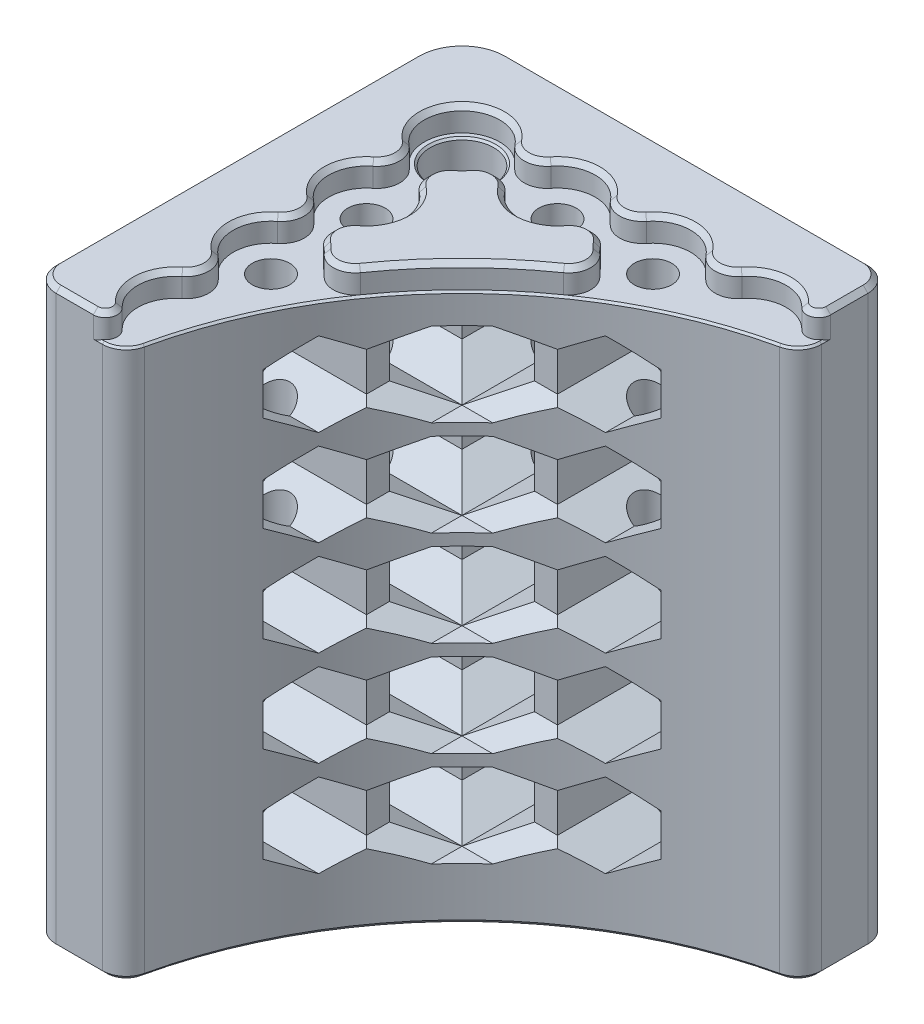
SolidWorks part; units mm, degrees
material "PET"
ref_plane "Front Plane" through (0, 0, 0) normal (0, 0, 1) x (1, 0, 0)
ref_plane "Top Plane" through (0, 0, 0) normal (0, 1, 0) x (1, 0, 0)
ref_plane "Right Plane" through (0, 0, 0) normal (1, 0, 0) x (0, 0, -1)
sketch "Sketch2" plane through (0, 0, 0) normal (0, 1, 0) x (1, 0, 0)
  line L0 (0, 0) -> (0, -53.975)
  line L1 (0, 0) -> (53.975, 0)
  line L2 (57.15, -3.175) -> (57.15, -11.935)
  line L3 (3.175, -57.15) -> (9.3269, -57.15)
  circle A0 centre (66.675, -66.675) radius 55.5625
  circle A1 centre (53.975, -3.175) radius 3.175
  circle A2 centre (53.975, -9.3269) radius 3.175
  circle A3 centre (3.175, -53.975) radius 3.175
  circle A4 centre (9.3269, -53.975) radius 3.175
  circle A5 centre (6.35, -6.35) radius 6.35
  dimension "D2" = 111.125
  dimension "D3" = 6.35
  dimension "D6" = 6.35
  dimension "D7" = 12.7
  dimension "D1" = 53.975
  dimension "D4" = 66.675
  dimension "D5" = 66.675
extrude "Boss-Extrude1" add sketch "Sketch2" along normal blind 76.2 contours A4 A0 A2 A1 L1 L0 A3 | A4 A3 | A4 A3 L3 | A4 A3 | A2 A1 | A2 L2 A1 | A2 A1 | A3 A4 | A1 A2 | A5 region at (20.4992, 0, 20.4992) region at (6.35, 0, 6.35) region at (3.1546, 0, 53.975) region at (53.975, 0, 3.1546) region at (6.251, 0, 56.5266) region at (9.3473, 0, 53.975) region at (6.251, 0, 53.975) region at (56.5266, 0, 6.251) region at (53.975, 0, 6.251) region at (53.975, 0, 9.3473)
sketch "Sketch3" plane through (0, 0, 0) normal (-1, 0, 0) x (0, 0, 1)
  line L0 (6.35, 0) -> (53.975, 0) construction
  line L2 (0, 76.2) -> (0, 0) construction
  circle A0 centre (25.4, 12.7) radius 2.4892
  circle A1 centre (38.1, 12.7) radius 2.4892
  circle A2 centre (38.1, 25.4) radius 2.4892
  circle A3 centre (38.1, 38.1) radius 2.4892
  circle A4 centre (38.1, 50.8) radius 2.4892
  circle A5 centre (38.1, 63.5) radius 2.4892
  circle A6 centre (25.4, 25.4) radius 2.4892
  circle A7 centre (25.4, 38.1) radius 2.4892
  circle A8 centre (25.4, 50.8) radius 2.4892
  circle A9 centre (25.4, 63.5) radius 2.4892
  dimension "D1" = 4.9784
  dimension "D2" = 12.7
  dimension "D3" = 25.4
  dimension "D6" = 12.7
  dimension "D7" = 12.7
  dimension "D4" = 2
  dimension "D5" = 5
extrude "Cut-Extrude1" cut sketch "Sketch3" against normal blind 76.2
sketch "Sketch4" plane through (0, 0, 0) normal (0, 0, -1) x (-1, 0, 0)
  line L0 (-6.35, 0) -> (-53.975, 0) construction
  line L1 (-6.35, 76.2) -> (-6.35, 0) construction
  circle A0 centre (-25.4, 12.7) radius 2.4892
  circle A1 centre (-38.1, 12.7) radius 2.4892
  circle A2 centre (-38.1, 25.4) radius 2.4892
  circle A3 centre (-38.1, 38.1) radius 2.4892
  circle A4 centre (-38.1, 50.8) radius 2.4892
  circle A5 centre (-38.1, 63.5) radius 2.4892
  circle A6 centre (-25.4, 25.4) radius 2.4892
  circle A7 centre (-25.4, 38.1) radius 2.4892
  circle A8 centre (-25.4, 50.8) radius 2.4892
  circle A9 centre (-25.4, 63.5) radius 2.4892
  dimension "D1" = 4.9784
  dimension "D2" = 12.7
  dimension "D3" = 19.05
  dimension "D6" = 12.7
  dimension "D7" = 12.7
  dimension "D4" = 2
  dimension "D5" = 5
extrude "Cut-Extrude2" cut sketch "Sketch4" against normal blind 76.2
sketch "Sketch5" plane through (0, 76.2, 0) normal (0, 1, 0) x (1, 0, 0)
  line L0 (12.7, -12.7) -> (12.7, -25.4) construction
  line L1 (12.7, -25.4) -> (12.7, -38.1) construction
  line L2 (12.7, -12.7) -> (25.4, -12.7) construction
  line L3 (25.4, -12.7) -> (38.1, -12.7) construction
  line L4 (0, -6.35) -> (0, -53.975) construction
  line L5 (6.35, 0) -> (53.975, 0) construction
  circle A0 centre (12.7, -12.7) radius 4.2228
  circle A1 centre (25.4, -12.7) radius 2.4892
  circle A2 centre (38.1, -12.7) radius 2.4892
  circle A3 centre (12.7, -25.4) radius 2.4892
  circle A4 centre (12.7, -38.1) radius 2.4892
  dimension "D1" = 8.4455
  dimension "D2" = 4.9784
  dimension "D3" = 12.7
  dimension "D4" = 12.7
  dimension "D5" = 12.7
  dimension "D6" = 12.7
  dimension "D7" = 12.7
extrude "Cut-Extrude3" cut sketch "Sketch5" against normal through all contours A0 region at (12.7, 76.2, 12.7)
sketch "Sketch8" plane through (0, 76.2, 0) normal (0, 1, 0) x (1, 0, 0)
  circle A0 centre (12.7, -38.1) radius 2.4892 construction
  circle A1 centre (12.7, -25.4) radius 2.4892 construction
  circle A2 centre (38.1, -12.7) radius 2.4892 construction
  circle A3 centre (25.4, -12.7) radius 2.4892 construction
  circle A4 centre (12.7, -38.1) radius 2.4892
  circle A5 centre (12.7, -25.4) radius 2.4892
  circle A6 centre (38.1, -12.7) radius 2.4892
  circle A7 centre (25.4, -12.7) radius 2.4892
extrude "Cut-Extrude5" cut sketch "Sketch8" against normal blind 35.56
sketch "Sketch7" plane through (0, 76.2, 0) normal (0, 1, 0) x (1, 0, 0)
  line L0 (3.175, -57.15) -> (9.3269, -57.15) construction
  line L1 (6.35, 0) -> (53.975, 0) construction
  line L2 (57.15, -3.175) -> (57.15, -9.3269) construction
  line L3 (0, -6.35) -> (0, -53.975) construction
  line L4 (6.35, 0) -> (53.975, 0)
  line L5 (57.15, -3.175) -> (57.15, -9.3269)
  line L6 (3.175, -57.15) -> (9.3269, -57.15)
  line L7 (0, -6.35) -> (0, -53.975)
  circle A0 centre (12.7, -12.7) radius 5.0165
  circle A1 centre (25.4, -12.7) radius 5.0165
  circle A2 centre (38.1, -12.7) radius 5.0165
  circle A3 centre (12.7, -25.4) radius 5.0165
  circle A4 centre (12.7, -38.1) radius 5.0165
  arc A5 (9.6076, -21.45) -> (9.6076, -16.65) centre (7.7287, -19.05) ccw
  arc A6 (9.6076, -34.15) -> (9.6076, -29.35) centre (7.7287, -31.75) ccw
  arc A7 (29.35, -9.6076) -> (34.15, -9.6076) centre (31.75, -7.7287) ccw
  arc A8 (16.65, -9.6076) -> (21.45, -9.6076) centre (19.05, -7.7287) ccw
  arc A9 (9.6076, -46.85) -> (9.6076, -42.05) centre (7.7287, -44.45) ccw
  arc A10 (8.1249, -57.15) -> (9.2247, -54.4177) centre (8.1249, -55.5625) ccw
  arc A11 (9.6076, -46.85) -> (9.2247, -54.4177) centre (12.7, -50.8) ccw
  arc A12 (57.15, -3.175) -> (53.975, 0) centre (53.975, -3.175) ccw construction
  arc A13 (6.35, 0) -> (0, -6.35) centre (6.35, -6.35) ccw construction
  circle A14 centre (12.7, -25.4) radius 2.4892 construction
  arc A15 (9.3269, -57.15) -> (12.4268, -54.6615) centre (9.3269, -53.975) ccw construction
  arc A16 (54.6615, -12.4268) -> (12.4268, -54.6615) centre (66.675, -66.675) ccw construction
  arc A17 (0, -53.975) -> (3.175, -57.15) centre (3.175, -53.975) ccw construction
  arc A18 (57.15, -3.175) -> (53.975, 0) centre (53.975, -3.175) ccw
  arc A19 (6.35, 0) -> (0, -6.35) centre (6.35, -6.35) ccw
  arc A20 (54.6615, -12.4268) -> (57.15, -9.3269) centre (53.975, -9.3269) ccw
  arc A21 (9.3269, -57.15) -> (12.4268, -54.6615) centre (9.3269, -53.975) ccw
  arc A22 (54.6615, -12.4268) -> (12.4268, -54.6615) centre (66.675, -66.675) ccw
  arc A23 (0, -53.975) -> (3.175, -57.15) centre (3.175, -53.975) ccw
  arc A24 (54.4177, -9.2247) -> (46.85, -9.6076) centre (50.8, -12.7) ccw
  arc A25 (54.4177, -9.2247) -> (57.15, -8.1249) centre (55.5625, -8.1249) ccw
  arc A26 (42.05, -9.6076) -> (46.85, -9.6076) centre (44.45, -7.7287) ccw
  arc A27 (55.7937, -11.9294) -> (11.9294, -55.7937) centre (66.675, -66.675) ccw
  arc A28 (34.5329, -21.0421) -> (34.7825, -16.4629) centre (32.8508, -18.654) ccw
  arc A29 (16.4629, -34.7825) -> (21.0421, -34.5329) centre (18.654, -32.8508) ccw
  arc A30 (34.0868, -15.7099) -> (29.4132, -15.7099) centre (31.75, -17.4625) ccw
  arc A31 (15.7099, -29.4132) -> (15.7099, -34.0868) centre (17.4625, -31.75) ccw
  arc A32 (15.7099, -16.7132) -> (15.7099, -21.3868) centre (17.4625, -19.05) ccw
  arc A33 (21.3868, -15.7099) -> (16.7132, -15.7099) centre (19.05, -17.4625) ccw
  circle A34 centre (12.7, -38.1) radius 2.4892 construction
  circle A38 centre (38.1, -12.7) radius 2.4892 construction
  circle A39 centre (25.4, -12.7) radius 2.4892 construction
  arc A40 (54.6615, -12.4268) -> (57.15, -9.3269) centre (53.975, -9.3269) ccw construction
  circle M5 centre (12.7, -12.7) radius 4.2228
  arc M6 (54.6615, -12.4268) -> (57.15, -9.3269) centre (53.975, -9.3269) ccw
  line M7 (57.15, -9.3269) -> (57.15, -3.175)
  arc M14 (9.3269, -57.15) -> (12.4268, -54.6615) centre (9.3269, -53.975) ccw
  arc M15 (12.4268, -54.6615) -> (54.6615, -12.4268) centre (66.675, -66.675) cw
  circle M59 centre (12.7, -38.1) radius 2.4892
  circle M60 centre (25.4, -12.7) radius 2.4892
  circle M61 centre (38.1, -12.7) radius 2.4892
  circle M62 centre (12.7, -25.4) radius 2.4892
  dimension "D1" = 10.033
  dimension "D2" = 6.096
  dimension "D3" = 3.175
  dimension "D4" = 111.633
  dimension "D5" = 5.842
extrude "Cut-Extrude8" cut sketch "Sketch7" against normal blind 3.175 contours A0 M5 | A32 A0 A5 A3 | A3 M62 | A31 A3 A6 A4 | A4 M59 | A29 A4 A9 A11 A10 L6 A27 M14 | A27 A21 M6 M15 | A33 A1 A8 A0 | A1 M60 | A30 A2 A7 A1 | A28 A27 A20 A25 A24 A26 A2 M7 | A2 M61 region at (47.9531, 76.2, 12.1291) region at (12.1291, 76.2, 47.9531) region at (55.2271, 76.2, 12.177) region at (42.7083, 76.2, 11.1107) region at (31.75, 76.2, 12.6504) region at (7.8254, 76.2, 38.1) region at (30.0083, 76.2, 11.1107) region at (12.6504, 76.2, 31.75) region at (19.05, 76.2, 12.6504) region at (7.8254, 76.2, 25.4) region at (17.3083, 76.2, 11.1107) region at (12.6504, 76.2, 19.05)
ref_plane "Plane1" through (57.15, 0, 0) normal (1, 0, 0) x (0, 0, -1)
ref_plane "Plane2" through (0, 0, 57.15) normal (0, 0, 1) x (1, 0, 0)
sketch "Sketch9" plane through (57.15, 0, 0) normal (1, 0, 0) x (0, 0, -1)
  line L1 (-42.926, 66.2863) -> (-42.926, 60.7137)
  line L2 (-42.926, 60.7137) -> (-38.1, 57.9274)
  line L3 (-38.1, 57.9274) -> (-33.274, 60.7137)
  line L4 (-33.274, 60.7137) -> (-33.274, 66.2863)
  line L5 (-33.274, 66.2863) -> (-38.1, 69.0726)
  line L6 (-38.1, 69.0726) -> (-42.926, 66.2863)
  line L7 (-20.574, 66.2863) -> (-25.4, 69.0726)
  line L8 (-25.4, 69.0726) -> (-30.226, 66.2863)
  line L9 (-30.226, 66.2863) -> (-30.226, 60.7137)
  line L10 (-30.226, 60.7137) -> (-25.4, 57.9274)
  line L11 (-25.4, 57.9274) -> (-20.574, 60.7137)
  line L12 (-20.574, 60.7137) -> (-20.574, 66.2863)
  line L13 (-20.574, 53.5863) -> (-25.4, 56.3726)
  line L14 (-25.4, 56.3726) -> (-30.226, 53.5863)
  line L15 (-30.226, 53.5863) -> (-30.226, 48.0137)
  line L16 (-30.226, 48.0137) -> (-25.4, 45.2274)
  line L17 (-25.4, 45.2274) -> (-20.574, 48.0137)
  line L18 (-20.574, 48.0137) -> (-20.574, 53.5863)
  line L19 (-33.274, 53.5863) -> (-38.1, 56.3726)
  line L20 (-38.1, 56.3726) -> (-42.926, 53.5863)
  line L21 (-42.926, 53.5863) -> (-42.926, 48.0137)
  line L22 (-42.926, 48.0137) -> (-38.1, 45.2274)
  line L23 (-38.1, 45.2274) -> (-33.274, 48.0137)
  line L24 (-33.274, 48.0137) -> (-33.274, 53.5863)
  line L25 (-38.1, 43.6726) -> (-42.926, 40.8863)
  line L26 (-42.926, 40.8863) -> (-42.926, 35.3137)
  line L27 (-42.926, 35.3137) -> (-38.1, 32.5274)
  line L28 (-38.1, 32.5274) -> (-33.274, 35.3137)
  line L29 (-33.274, 35.3137) -> (-33.274, 40.8863)
  line L30 (-33.274, 40.8863) -> (-38.1, 43.6726)
  line L31 (-20.574, 40.8863) -> (-25.4, 43.6726)
  line L32 (-25.4, 43.6726) -> (-30.226, 40.8863)
  line L33 (-30.226, 40.8863) -> (-30.226, 35.3137)
  line L34 (-30.226, 35.3137) -> (-25.4, 32.5274)
  line L35 (-25.4, 32.5274) -> (-20.574, 35.3137)
  line L36 (-20.574, 35.3137) -> (-20.574, 40.8863)
  line L37 (-20.574, 28.1863) -> (-25.4, 30.9726)
  line L38 (-25.4, 30.9726) -> (-30.226, 28.1863)
  line L39 (-30.226, 28.1863) -> (-30.226, 22.6137)
  line L40 (-30.226, 22.6137) -> (-25.4, 19.8274)
  line L41 (-25.4, 19.8274) -> (-20.574, 22.6137)
  line L42 (-20.574, 22.6137) -> (-20.574, 28.1863)
  line L43 (-33.274, 28.1863) -> (-38.1, 30.9726)
  line L44 (-38.1, 30.9726) -> (-42.926, 28.1863)
  line L45 (-42.926, 28.1863) -> (-42.926, 22.6137)
  line L46 (-42.926, 22.6137) -> (-38.1, 19.8274)
  line L47 (-38.1, 19.8274) -> (-33.274, 22.6137)
  line L48 (-33.274, 22.6137) -> (-33.274, 28.1863)
  line L49 (-38.1, 18.2726) -> (-42.926, 15.4863)
  line L50 (-42.926, 15.4863) -> (-42.926, 9.9137)
  line L51 (-42.926, 9.9137) -> (-38.1, 7.1274)
  line L52 (-38.1, 7.1274) -> (-33.274, 9.9137)
  line L53 (-33.274, 9.9137) -> (-33.274, 15.4863)
  line L54 (-33.274, 15.4863) -> (-38.1, 18.2726)
  line L55 (-20.574, 15.4863) -> (-25.4, 18.2726)
  line L56 (-25.4, 18.2726) -> (-30.226, 15.4863)
  line L57 (-30.226, 15.4863) -> (-30.226, 9.9137)
  line L58 (-30.226, 9.9137) -> (-25.4, 7.1274)
  line L59 (-25.4, 7.1274) -> (-20.574, 9.9137)
  line L60 (-20.574, 9.9137) -> (-20.574, 15.4863)
  circle A0 centre (-38.1, 63.5) radius 4.826 construction
  circle A1 centre (-25.4, 63.5) radius 4.826 construction
  circle A2 centre (-25.4, 50.8) radius 4.826 construction
  circle A3 centre (-38.1, 50.8) radius 4.826 construction
  circle A4 centre (-38.1, 38.1) radius 4.826 construction
  circle A5 centre (-25.4, 38.1) radius 4.826 construction
  circle A6 centre (-25.4, 25.4) radius 4.826 construction
  circle A7 centre (-38.1, 25.4) radius 4.826 construction
  circle A8 centre (-38.1, 12.7) radius 4.826 construction
  circle A9 centre (-25.4, 12.7) radius 4.826 construction
  point P91 (-33.274, 38.1)
  dimension "D1" = 9.652
extrude "Cut-Extrude6" cut sketch "Sketch9" against normal offset from surface (47.625 mm away) 9.525 up to face at (0, 63.5, 40.5892)
chamfer "Chamfer3" distance 0.254 angle 45 6 edges at (12.7, 73.025, 16.9228) (57.15, 73.025, 8.7259) (56.4509, 73.025, 11.3145) (8.7259, 73.025, 57.15) (27.3864, 73.025, 27.3864) (11.3145, 73.025, 56.4509)
chamfer "Chamfer4" distance 0.635 angle 45 45 edges at (34.4154, 76.2, 16.1042) (31.75, 76.2, 14.5415) (35.7675, 76.2, 18.813) (25.4, 76.2, 17.7165) (19.05, 76.2, 14.5415) (16.2472, 76.2, 16.2472) (27.2068, 76.2, 27.2068) (18.813, 76.2, 35.7675) (16.1042, 76.2, 34.4154) (14.5415, 76.2, 31.75) (17.7165, 76.2, 25.4) (14.5415, 76.2, 19.05) (10.7767, 76.2, 19.05) (9.1528, 76.2, 9.1528) (19.05, 76.2, 10.7767) (25.4, 76.2, 7.6835) (31.75, 76.2, 10.7767) (38.1, 76.2, 7.6835) (44.45, 76.2, 10.7767) (50.5465, 76.2, 7.6899) (56.1553, 76.2, 9.5976) (57.15, 76.2, 5.65) (56.2201, 76.2, 0.9299) (30.1625, 76.2, 0) (1.8599, 76.2, 1.8599) (0, 76.2, 30.1625) (0.9299, 76.2, 56.2201) (5.65, 76.2, 57.15) (9.5976, 76.2, 56.1553) (7.6899, 76.2, 50.5465) (10.7767, 76.2, 44.45) (7.6835, 76.2, 38.1) (10.7767, 76.2, 31.75) (7.6835, 76.2, 25.4) (12.7, 0, 16.9228) (56.2201, 0, 0.9299) (57.15, 0, 6.251) (56.4509, 0, 11.3145) (30.1625, 0, 0) (1.8599, 0, 1.8599) (0, 0, 30.1625) (0.9299, 0, 56.2201) (6.251, 0, 57.15) (27.3864, 0, 27.3864) (11.3145, 0, 56.4509)
sketch "Sketch13" plane through (0, 0, 57.15) normal (0, 0, 1) x (1, 0, 0)
  line L1 (25.4, 69.0726) -> (20.574, 66.2863)
  line L2 (20.574, 66.2863) -> (20.574, 60.7137)
  line L3 (20.574, 60.7137) -> (25.4, 57.9274)
  line L4 (25.4, 57.9274) -> (30.226, 60.7137)
  line L5 (30.226, 60.7137) -> (30.226, 66.2863)
  line L6 (30.226, 66.2863) -> (25.4, 69.0726)
  line L7 (42.926, 66.2863) -> (38.1, 69.0726)
  line L8 (38.1, 69.0726) -> (33.274, 66.2863)
  line L9 (33.274, 66.2863) -> (33.274, 60.7137)
  line L10 (33.274, 60.7137) -> (38.1, 57.9274)
  line L11 (38.1, 57.9274) -> (42.926, 60.7137)
  line L12 (42.926, 60.7137) -> (42.926, 66.2863)
  line L13 (42.926, 53.5863) -> (38.1, 56.3726)
  line L14 (38.1, 56.3726) -> (33.274, 53.5863)
  line L15 (33.274, 53.5863) -> (33.274, 48.0137)
  line L16 (33.274, 48.0137) -> (38.1, 45.2274)
  line L17 (38.1, 45.2274) -> (42.926, 48.0137)
  line L18 (42.926, 48.0137) -> (42.926, 53.5863)
  line L19 (30.226, 53.5863) -> (25.4, 56.3726)
  line L20 (25.4, 56.3726) -> (20.574, 53.5863)
  line L21 (20.574, 53.5863) -> (20.574, 48.0137)
  line L22 (20.574, 48.0137) -> (25.4, 45.2274)
  line L23 (25.4, 45.2274) -> (30.226, 48.0137)
  line L24 (30.226, 48.0137) -> (30.226, 53.5863)
  line L25 (30.226, 40.8863) -> (25.4, 43.6726)
  line L26 (25.4, 43.6726) -> (20.574, 40.8863)
  line L27 (20.574, 40.8863) -> (20.574, 35.3137)
  line L28 (20.574, 35.3137) -> (25.4, 32.5274)
  line L29 (25.4, 32.5274) -> (30.226, 35.3137)
  line L30 (30.226, 35.3137) -> (30.226, 40.8863)
  line L31 (42.926, 40.8863) -> (38.1, 43.6726)
  line L32 (38.1, 43.6726) -> (33.274, 40.8863)
  line L33 (33.274, 40.8863) -> (33.274, 35.3137)
  line L34 (33.274, 35.3137) -> (38.1, 32.5274)
  line L35 (38.1, 32.5274) -> (42.926, 35.3137)
  line L36 (42.926, 35.3137) -> (42.926, 40.8863)
  line L37 (42.926, 28.1863) -> (38.1, 30.9726)
  line L38 (38.1, 30.9726) -> (33.274, 28.1863)
  line L39 (33.274, 28.1863) -> (33.274, 22.6137)
  line L40 (33.274, 22.6137) -> (38.1, 19.8274)
  line L41 (38.1, 19.8274) -> (42.926, 22.6137)
  line L42 (42.926, 22.6137) -> (42.926, 28.1863)
  line L43 (30.226, 28.1863) -> (25.4, 30.9726)
  line L44 (25.4, 30.9726) -> (20.574, 28.1863)
  line L45 (20.574, 28.1863) -> (20.574, 22.6137)
  line L46 (20.574, 22.6137) -> (25.4, 19.8274)
  line L47 (25.4, 19.8274) -> (30.226, 22.6137)
  line L48 (30.226, 22.6137) -> (30.226, 28.1863)
  line L49 (30.226, 15.4863) -> (25.4, 18.2726)
  line L50 (25.4, 18.2726) -> (20.574, 15.4863)
  line L51 (20.574, 15.4863) -> (20.574, 9.9137)
  line L52 (20.574, 9.9137) -> (25.4, 7.1274)
  line L53 (25.4, 7.1274) -> (30.226, 9.9137)
  line L54 (30.226, 9.9137) -> (30.226, 15.4863)
  line L55 (42.926, 15.4863) -> (38.1, 18.2726)
  line L56 (38.1, 18.2726) -> (33.274, 15.4863)
  line L57 (33.274, 15.4863) -> (33.274, 9.9137)
  line L58 (33.274, 9.9137) -> (38.1, 7.1274)
  line L59 (38.1, 7.1274) -> (42.926, 9.9137)
  line L60 (42.926, 9.9137) -> (42.926, 15.4863)
  circle A0 centre (25.4, 63.5) radius 4.826 construction
  circle A1 centre (38.1, 63.5) radius 4.826 construction
  circle A2 centre (38.1, 50.8) radius 4.826 construction
  circle A3 centre (25.4, 50.8) radius 4.826 construction
  circle A4 centre (25.4, 38.1) radius 4.826 construction
  circle A5 centre (38.1, 38.1) radius 4.826 construction
  circle A6 centre (38.1, 25.4) radius 4.826 construction
  circle A7 centre (25.4, 25.4) radius 4.826 construction
  circle A8 centre (25.4, 12.7) radius 4.826 construction
  circle A9 centre (38.1, 12.7) radius 4.826 construction
  dimension "D1" = 9.652
extrude "Cut-Extrude9" cut sketch "Sketch13" against normal offset from surface (47.625 mm away) 9.525 up to face at (35.6108, 63.5, 0)
sketch "Sketch14" plane through (57.15, 0, 0) normal (1, 0, 0) x (0, 0, -1)
  line L0 (0, 75.565) -> (0, 0.635) construction
  line L1 (-25.4, 69.0726) -> (-29.4787, 69.0726)
  line L2 (-25.4, 69.0726) -> (-25.4, 7.1274)
  line L3 (-25.4, 7.1274) -> (-29.4787, 7.1274)
  line L4 (-29.4787, 69.0726) -> (-29.4787, 7.1274)
  line L5 (-27.3864, 67.9257) -> (-25.4, 69.0726) construction
  line L6 (-25.4, 8.2743) -> (-29.4787, 8.2743)
  line L7 (-29.4787, 17.1257) -> (-25.4, 17.1257)
  line L8 (-29.4787, 20.9743) -> (-25.4, 20.9743)
  line L9 (-29.4787, 45.2274) -> (-25.4, 45.2274)
  line L10 (-29.4787, 29.8257) -> (-25.4, 29.8257)
  line L11 (-25.4, 43.6726) -> (-29.4787, 43.6726)
  line L12 (-29.4787, 33.6743) -> (-25.4, 33.6743)
  line L13 (-29.4787, 32.5274) -> (-25.4, 32.5274)
  line L14 (-29.4787, 46.3743) -> (-25.4, 46.3743)
  line L15 (-29.4787, 42.5257) -> (-25.4, 42.5257)
  line L16 (-29.4787, 55.2257) -> (-25.4, 55.2257)
  line L17 (-29.4787, 59.0743) -> (-25.4, 59.0743)
  line L18 (-29.4787, 67.9257) -> (-25.4, 67.9257)
  line L19 (-25.4, 57.9274) -> (-29.4787, 57.9274)
  line L20 (-29.4787, 56.3726) -> (-25.4, 56.3726)
  line L21 (-25.4, 30.9726) -> (-29.4787, 30.9726)
  line L22 (-29.4787, 19.8274) -> (-25.4, 19.8274)
  line L23 (-25.4, 18.2726) -> (-29.4787, 18.2726)
  dimension "D1" = 25.4
extrude "Cut-Extrude10" cut sketch "Sketch14" against normal up to vertex (31.75 mm away) contours L2 L6 L4 L3 | L2 L23 L4 L7 | L4 L22 L2 L8 | L4 L13 L2 L12 | L2 L21 L4 L10 | L14 L4 L9 L2 | L4 L15 L2 L11 | L19 L2 L17 L4 | L20 L4 L16 L2 | L4 L18 L2 L1 region at (57.15, 68.4992, 27.4393) region at (57.15, 58.5008, 27.4393) region at (57.15, 55.7992, 27.4393) region at (57.15, 45.8008, 27.4393) region at (57.15, 43.0992, 27.4393) region at (57.15, 33.1008, 27.4393) region at (57.15, 30.3992, 27.4393) region at (57.15, 20.4008, 27.4393) region at (57.15, 17.6992, 27.4393) region at (57.15, 7.7008, 27.4393) up to point (25.4, 57.9274, 25.4)
